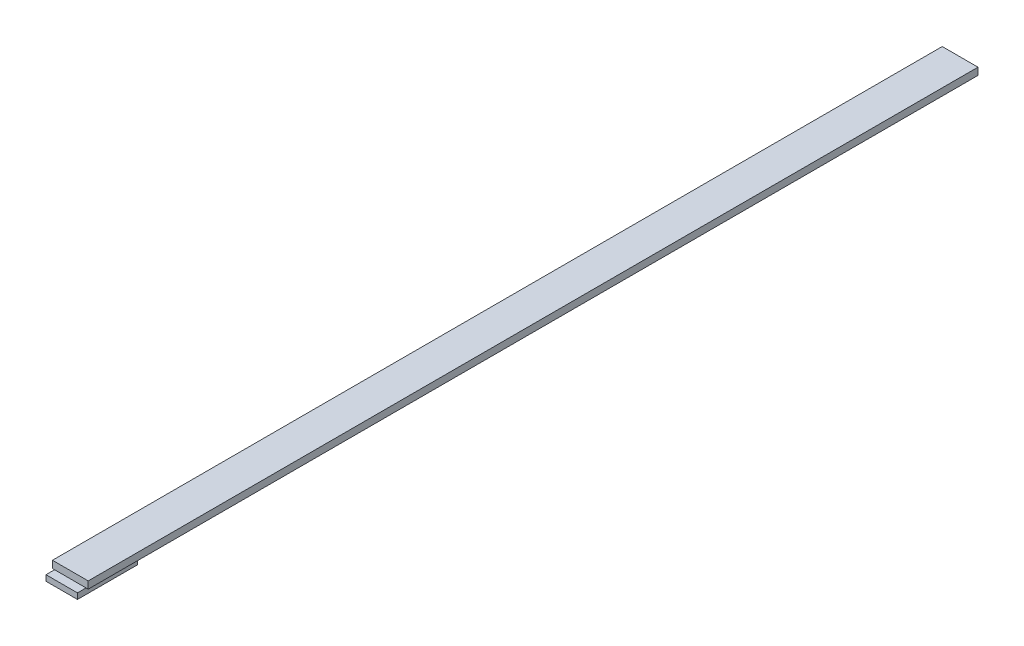
SolidWorks part; units mm, degrees
material "6061 Alloy"
ref_plane "Front Plane" through (0, 0, 0) normal (0, 0, 1) x (1, 0, 0)
ref_plane "Top Plane" through (0, 0, 0) normal (0, 1, 0) x (1, 0, 0)
ref_plane "Right Plane" through (0, 0, 0) normal (1, 0, 0) x (0, 0, -1)
sketch "Sketch1" plane through (0, 0, 0) normal (0, 0, 1) x (1, 0, 0)
  line L0 (6.25, 2.5) -> (6.25, 0) construction
  line L1 (0, 0) -> (12.5, 0)
  line L2 (0, 0) -> (0, 2.5)
  line L3 (0, 2.5) -> (12.5, 2.5)
  line L4 (12.5, 0) -> (12.5, 2.5)
  dimension "D1" = 12.5
  dimension "D2" = 2.5
extrude "Boss-Extrude1" add sketch "Sketch1" along normal blind 311
sketch "Sketch3" plane through (0, 2.5, 0) normal (0, 1, 0) x (1, 0, 0)
  line L0 (6.323, 0) -> (6.323, -37) construction
  line L1 (12.5, 0) -> (0, 0) construction
  dimension "D1" = 37
  dimension "D2" = 0
sketch "Sketch4" plane through (0, 0, 0) normal (0, -1, 0) x (1, 0, 0)
  line L0 (0, 311) -> (12.5, 311) construction
  line L1 (0.75, 314) -> (11.75, 314)
  line L2 (0.75, 314) -> (0.75, 293)
  line L3 (0.75, 293) -> (11.75, 293)
  line L4 (11.75, 314) -> (11.75, 293)
  line L5 (6.25, 314) -> (6.25, 311) construction
  point P6 (6.25, 311)
  point P7 (6.25, 314)
  dimension "D1" = 21
  dimension "D2" = 11
  dimension "D3" = 3
  dimension "D4" = 0
extrude "Boss-Extrude2" add sketch "Sketch4" along normal blind 2
